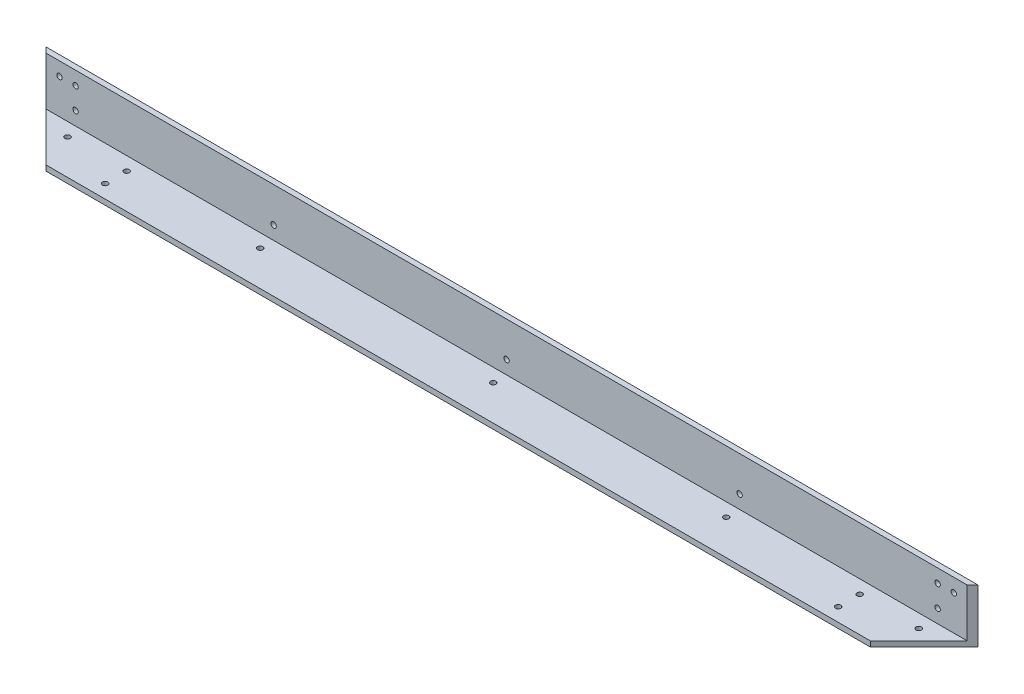
SolidWorks part; units mm, degrees
ref_plane "Front Plane" through (0, 0, 0) normal (0, 0, 1) x (1, 0, 0)
ref_plane "Top Plane" through (0, 0, 0) normal (0, 1, 0) x (1, 0, 0)
ref_plane "Right Plane" through (0, 0, 0) normal (1, 0, 0) x (0, 0, -1)
sketch "Sketch1" plane through (0, 0, 0) normal (1, 0, 0) x (0, 0, -1)
  line L0 (0, 0) -> (-31.75, 0)
  line L1 (-31.75, 0) -> (-31.75, 3.175)
  line L2 (-31.75, 3.175) -> (-3.175, 3.175)
  line L3 (-3.175, 3.175) -> (-3.175, 31.75)
  line L4 (-3.175, 31.75) -> (0, 31.75)
  line L5 (0, 31.75) -> (0, 0)
  dimension "LHeight" = 31.75
  dimension "LWidth" = 31.75
  dimension "LMaterialThickness" = 3.175
  dimension "D1" = 28.575
  dimension "D2" = 28.575
  dimension "D3" = 3.175
extrude "Boss-Extrude1" add sketch "Sketch1" along normal blind 550
chamfer "Chamfer6" distance 31.75 angle 45 1 edges at (550, 1.5875, 31.75)
chamfer "Chamfer7" distance 31.75 angle 45 1 edges at (0, 1.5875, 31.75)
sketch "TopHoles-Sketch3" plane through (0, 3.175, 0) normal (0, 1, 0) x (1, 0, 0)
  line L1 (518.25, -31.75) -> (31.75, -31.75) construction
  line L2 (550, 0) -> (0, 0) construction
  circle A5 centre (58.7375, -23.8125) radius 1.5875
  circle A6 centre (491.2625, -23.8125) radius 1.5875
  circle A9 centre (491.2625, -11.1125) radius 1.5875
  circle A10 centre (58.7375, -11.1125) radius 1.5875
  circle A11 centre (526.1875, -11.1125) radius 1.5875
  circle A12 centre (23.8125, -11.1125) radius 1.5875
  circle A13 centre (137.5, -11.1125) radius 1.5875
  circle A14 centre (275, -11.1125) radius 1.5875
  circle A15 centre (412.5, -11.1125) radius 1.5875
  dimension "D8" = 137.5
  dimension "D10" = 137.5
  dimension "D9" = 3.175
  dimension "D12" = 7.9375
  dimension "D2" = 11.1125
  dimension "D6" = 23.8125
  dimension "D3" = 23.8125
  dimension "D5" = 12.7
  dimension "D4" = 34.925
  dimension "D7" = 34.925
  dimension "D11" = 137.5
extrude "TopHoles-Cut-Extrude2" cut sketch "TopHoles-Sketch3" against normal through all
sketch "RightHoles-Sketch4" plane through (0, 0, 3.175) normal (0, 0, 1) x (1, 0, 0)
  line L1 (550, 0) -> (0, 0) construction
  line L3 (550, 31.75) -> (0, 31.75) construction
  line L4 (0, 0) -> (0, 31.75) construction
  line L5 (550, 0) -> (550, 31.75) construction
  circle A1 centre (11.1125, 23.8125) radius 1.5875
  circle A3 centre (529.3625, 23.8125) radius 1.5875
  circle A4 centre (20.6375, 23.8125) radius 1.5875
  circle A5 centre (538.8875, 23.8125) radius 1.5875
  circle A7 centre (20.6375, 11.1125) radius 1.5875
  circle A8 centre (529.3625, 11.1125) radius 1.5875
  circle A10 centre (137.5, 11.1125) radius 1.5875
  circle A11 centre (275, 11.1125) radius 1.5875
  circle A12 centre (412.5, 11.1125) radius 1.5875
  dimension "D2" = 3.175
  dimension "D4" = 7.9375
  dimension "D1" = 11.1125
  dimension "D6" = 20.6375
  dimension "D3" = 11.1125
  dimension "D5" = 20.6375
  dimension "D8" = 137.5
  dimension "D9" = 137.5
  dimension "D10" = 137.5
  dimension "D7" = 11.1125
extrude "RightHoles-Cut-Extrude3" cut sketch "RightHoles-Sketch4" against normal through all
equation "\"TopRailWidth\"= 1.25in"
equation "\"TopRailHeight\"= 1.25in"
equation "\"RailThickness\"= .125in'Spec"
equation "\"SideRailHoleY1FromEdge\"= \"HoleOffsetFromEdge\""
equation "\"SideRailHoleX1FromSide\"= \"HoleOffsetFromSide\""
equation "\"SideRailLength\"= 550mm"
equation "\"VSWidth\"= 1.25in'Spec"
equation "\"HoleOffsetFromEdge\"= \"RailThickness\" * 2.5"
equation "\"HoleOffsetFromSide\"= \"RailThickness\" * 3.5"
equation "\"TopHoleY1FromSide\"= \"HoleOffsetFromSide\""
equation "\"TopHoleX1FromEdge\"= \"TopCBWidth\" - \"HoleOffsetFromEdge\"'Equals 20.6375"
equation "\"TopCBWidth\"= \"TopRailWidth\" - \"RailThickness\"'Equals 28.575"
equation "\"SideRailHoleX2FromSide\"= \"VSWidth\" - \"HoleOffsetFromEdge\" - \"RailThickness\"'Equals 20.6375"
equation "\"FasteningHoleDiameter\"= .125in"
equation "\"SideRailHoleY2FromSide\"= \"HoleOffsetFromSide\""
equation "\"D2@RightHoles-Sketch4\"=\"FasteningHoleDiameter\""
equation "\"LWidth@Sketch1\"=\"TopRailWidth\""
equation "\"LHeight@Sketch1\"=\"TopRailHeight\""
equation "\"LMaterialThickness@Sketch1\"=\"RailThickness\""
equation "\"D1@Boss-Extrude1\"=\"SideRailLength\""
equation "\"D2@TopHoles-Sketch3\"=\"TopHoleY1FromSide\""
equation "\"D9@TopHoles-Sketch3\" = \"FasteningHoleDiameter\""
equation "\"D4@RightHoles-Sketch4\"=\"SideRailHoleY1FromEdge\""
equation "\"D1@Chamfer6\"=\"TopRailWidth\""
equation "\"D1@Chamfer7\"=\"TopRailWidth\""
equation "\"D1@RightHoles-Sketch4\"=\"SideRailHoleX1FromSide\""
equation "\"D6@RightHoles-Sketch4\"=\"SideRailHoleX2FromSide\""
equation "\"D3@RightHoles-Sketch4\"=\"SideRailHoleX1FromSide\""
equation "\"D5@RightHoles-Sketch4\"=\"SideRailHoleX2FromSide\""
equation "\"TopHoleX2FromX1\"= \"TopCBLength\" - \"TopHoleX1FromEdge\" - \"HoleOffsetFromEdge\"'Equals 34.925"
equation "\"TopHoleY2FromY1\"= \"TopCBWidth\" - \"TopHoleY1FromEdge\" - \"HoleOffsetFromEdge\"'Equals 12.7"
equation "\"D3@TopHoles-Sketch3\"=\"TopHoleX1FromEdge\" + \"RailThickness\""
equation "\"D6@TopHoles-Sketch3\"=\"TopHoleX1FromEdge\" + \"RailThickness\""
equation "\"D5@TopHoles-Sketch3\"=\"TopHoleY2FromY1\""
equation "\"TopCBLength\"= \"TopRailWidth\" * 2'Equals 63.5"
equation "\"TopHoleY1FromEdge\"= \"HoleOffsetFromEdge\""
equation "\"D4@TopHoles-Sketch3\"=\"TopHoleX2FromX1\""
equation "\"D7@TopHoles-Sketch3\"=\"TopHoleX2FromX1\""
equation "\"LeftOrRightEnclosureOffsets\"= \"SideRailLength\" / 4"
equation "\"D8@TopHoles-Sketch3\"=\"LeftOrRightEnclosureOffsets\""
equation "\"D10@TopHoles-Sketch3\"=\"LeftOrRightEnclosureOffsets\""
equation "\"D11@TopHoles-Sketch3\"=\"LeftOrRightEnclosureOffsets\""
equation "\"D8@RightHoles-Sketch4\"=\"LeftOrRightEnclosureOffsets\""
equation "\"D9@RightHoles-Sketch4\"=\"LeftOrRightEnclosureOffsets\""
equation "\"D10@RightHoles-Sketch4\"=\"LeftOrRightEnclosureOffsets\""
equation "\"D7@RightHoles-Sketch4\"=\"SideRailHoleY2FromSide\""
